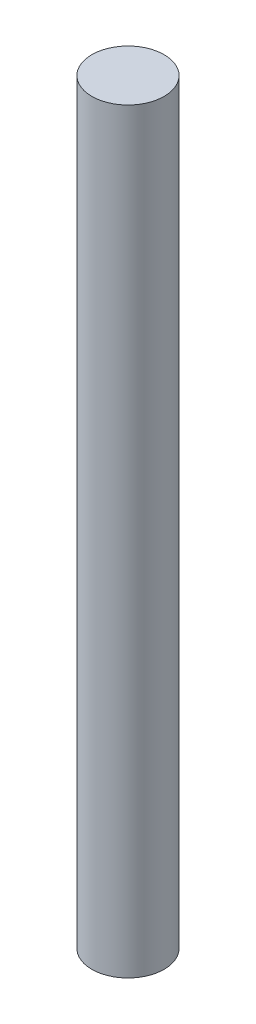
SolidWorks part; units mm, degrees
material "Nylon 6/10"
ref_plane "Front Plane" through (0, 0, 0) normal (0, 0, 1) x (1, 0, 0)
ref_plane "Top Plane" through (0, 0, 0) normal (0, 1, 0) x (1, 0, 0)
ref_plane "Right Plane" through (0, 0, 0) normal (1, 0, 0) x (0, 0, -1)
ref_axis "Axis1" through (0, 0, -88.99) along (0, 0, 1)
ref_axis "Axis2" through (0, -55, 0) along (0, 1, 0)
ref_axis "Axis3" through (-88.99, 0, 0) along (1, 0, 0)
sketch "Sketch1" plane through (0, 0, 0) normal (0, 1, 0) x (1, 0, 0)
  circle A0 centre (0, 0) radius 7.9375
  dimension "D1" = 15.875
extrude "Boss-Extrude1" add sketch "Sketch1" along normal blind 166
